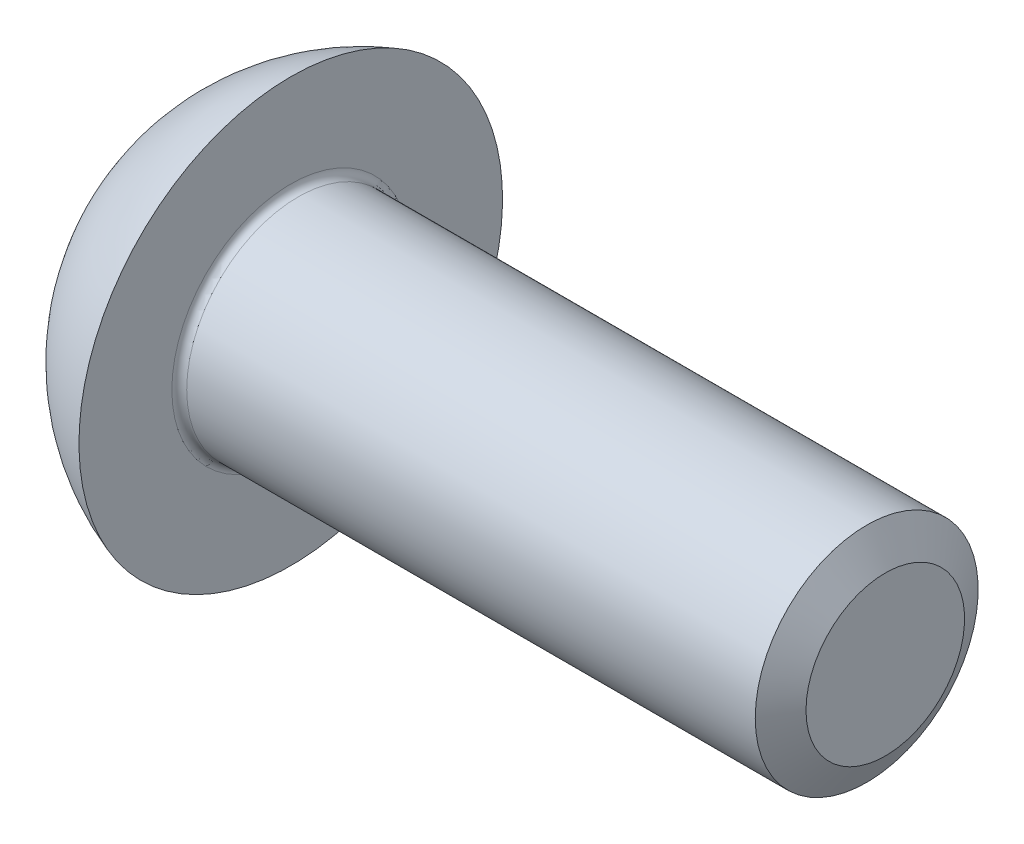
SolidWorks part; units mm, degrees
ref_plane "前视基准面" through (0, 0, 0) normal (0, 0, 1) x (1, 0, 0)
ref_plane "上视基准面" through (0, 0, 0) normal (0, 1, 0) x (1, 0, 0)
ref_plane "右视基准面" through (0, 0, 0) normal (1, 0, 0) x (0, 0, -1)
sketch "尺寸草图" plane through (0, 0, 0) normal (0, 0, 1) x (1, 0, 0)
  line L0 (0, 0) -> (8, 0) construction
  line L1 (8, 0) -> (8, 1.5) construction
  line L2 (8, 1.5) -> (7.5, 1.5) construction
  line L3 (0, 0) -> (0, 2.85) construction
  point P3 (1, 0)
  point P6 (8, 1.8)
  point P7 (0, 0.55)
  point P9 (1.65, 0)
  point P10 (1.75, 0)
  point P11 (8, 1)
  point P12 (2.79, 0)
  point P13 (2.99, 0)
  dimension "l" = 8
  dimension "d" = 3
  dimension "P" = 0.5
  dimension "a" = 1
  dimension "da" = 3.6
  dimension "dk" = 5.7
  dimension "e" = 2.3
  dimension "K" = 1.65
  dimension "r" = 0.1
  dimension "s" = 2
  dimension "t" = 1.04
  dimension "w" = 0.2
sketch "草图1" plane through (0, 0, 0) normal (0, 0, 1) x (1, 0, 0)
  line L0 (-9.65, 0) -> (0, 0) construction
  line L1 (0, 1.5) -> (-7.9, 1.5)
  line L2 (-8, 1.6) -> (-8, 2.85)
  line L3 (-9.65, 0) -> (-9.65, 1.5)
  line L4 (0, 1.5) -> (0, 0)
  line L5 (-9.65, 0) -> (0, 0)
  arc A0 (-8, 2.85) -> (-9.65, 1.5) centre (-7.0455, 0) ccw
  arc A1 (-7.9, 1.5) -> (-8, 1.6) centre (-7.9, 1.6) cw
  point P10 (-8, 1.5)
  dimension "r" = 0.1
  dimension "d" = 3
  dimension "dk" = 5.7
  dimension "k" = 1.65
  dimension "l" = 8
revolve "旋转1" add sketch "草图1" angle 360 about L0
cosmetic thread "装饰螺纹线1" parameters "D1"=7, "D2"=2.58
sketch "草图2" plane through (-9.65, 0, 0) normal (-1, 0, 0) x (0, 0, 1)
  line L1 (0, 1.1547) -> (-1, 0.5774)
  line L2 (-1, 0.5774) -> (-1, -0.5774)
  line L3 (-1, -0.5774) -> (0, -1.1547)
  line L4 (0, -1.1547) -> (1, -0.5774)
  line L5 (1, -0.5774) -> (1, 0.5774)
  line L6 (1, 0.5774) -> (0, 1.1547)
  circle A0 centre (0, 0) radius 1 construction
  dimension "s" = 2
extrude "切除-拉伸1" cut sketch "草图2" against normal blind 1.65
sketch "草图6" plane through (0, 0, 0) normal (0, 0, 1) x (1, 0, 0)
  line L0 (-8.61, 1.1547) -> (-8, 0)
  line L1 (-7.7, 1.1547) -> (-7.7, 0)
  line L2 (-7.7, 1.1547) -> (-8.61, 1.1547)
  line L3 (-9.65, 0) -> (-8, 0) construction
  line L4 (-7.7, 0) -> (-8, 0)
  line L5 (-9.65, 0) -> (-11.95, 0) construction
  dimension "t" = 1.04
  dimension "e-s" = 0.3
  dimension "k" = 1.65
  dimension "e" = 2.3
revolve "旋转2" add sketch "草图6" angle 360 about L3
sketch "草图7" plane through (0, 0, 0) normal (0, 0, 1) x (1, 0, 0)
  line L3 (-9.65, 1.1547) -> (-9.35, 0)
  line L4 (-9.65, 0) -> (-9.35, 0) construction
  line L7 (-9.65, 1.1547) -> (-9.65, 0)
  line L8 (-9.65, 0) -> (-9.35, 0)
  dimension "e-s" = 0.3
revolve "切除-旋转5" cut sketch "草图7" angle 360 about L4
sketch "草图4" plane through (0, 0, 0) normal (0, 0, 1) x (1, 0, 0)
  line L0 (-0.25, 1.5) -> (0, 1.067)
  line L1 (-0.25, 1.5) -> (0.25, 1.5)
  line L2 (0.25, 1.5) -> (0, 1.067)
  line L4 (0, -1.5) -> (0, 1.5) construction
  line L5 (-0.25, 0) -> (0.25, 0) construction
  dimension "d" = 1.5
  dimension "p" = 0.5
revolve "切除-旋转1" cut sketch "草图4" angle 360 about L5
ref_axis "基准轴1" through (-8.1887, 0, 0) along (1, 0, 0)
pattern_linear "阵列(线性)1" [suppressed] count 14 spacing 0.5 along (-1, 0, 0) of bodies 104
